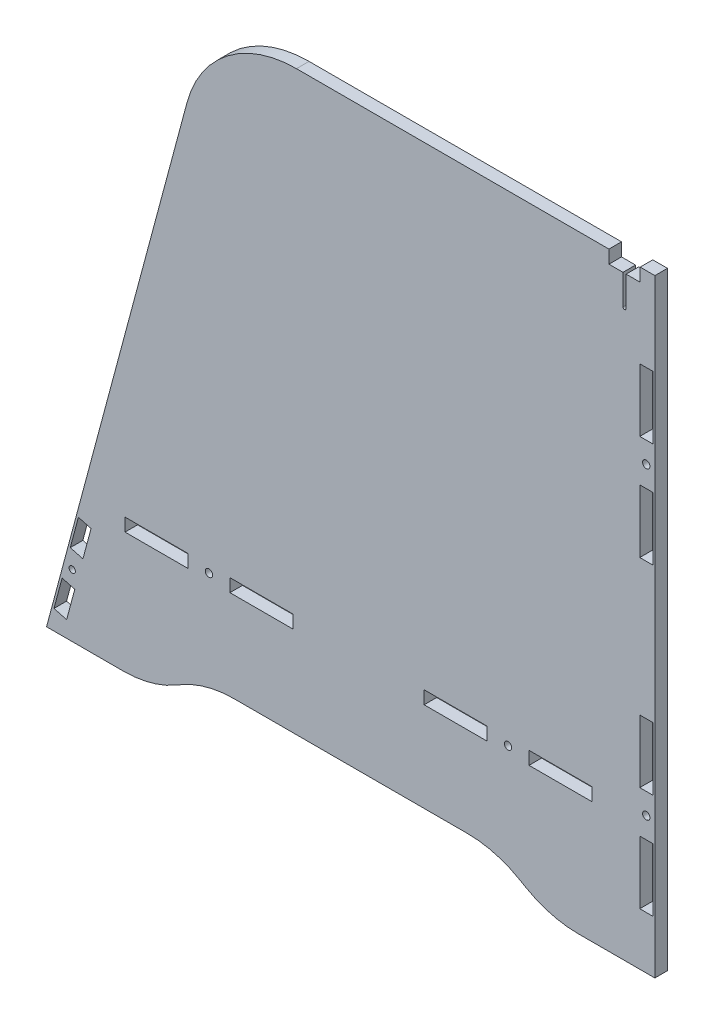
SolidWorks part; units mm, degrees
ref_plane "Plano frontal" through (0, 0, 0) normal (0, 0, 1) x (1, 0, 0)
ref_plane "Plano superior" through (0, 0, 0) normal (0, 1, 0) x (1, 0, 0)
ref_plane "Plano direito" through (0, 0, 0) normal (1, 0, 0) x (0, 0, -1)
sketch "Esboço1" plane through (0, 0, 0) normal (0, 0, 1) x (1, 0, 0)
  line L0 (125, -165) -> (75, -165)
  line L1 (75, -165) -> (49.0192, -150)
  line L2 (49.0192, -150) -> (-89.0192, -150)
  line L3 (-89.0192, -150) -> (-115, -165)
  line L4 (-115, -165) -> (-165, -165)
  line L5 (-165, -165) -> (-87.2947, 125)
  line L6 (-87.2947, 125) -> (125, 125)
  line L7 (125, 125) -> (125, -165)
  line L8 (-147.5833, -100) -> (125, -100) construction
  line L9 (-27.2947, 124) -> (65, 117.8) construction
  line L10 (125, -165) -> (-165, -165) construction
  line L11 (125, -165) -> (125, 125)
  line L12 (125, 125) -> (-165, 125) construction
  line L13 (-165, -165) -> (-165, 125) construction
  line L14 (-57.2947, 124) -> (-27.2947, 124) construction
  line L15 (-57.2947, 124) -> (-57.2947, 117.8) construction
  line L16 (-57.2947, 117.8) -> (-27.2947, 117.8) construction
  line L17 (-27.2947, 124) -> (-27.2947, 117.8) construction
  line L18 (65, 124) -> (95, 124) construction
  line L19 (65, 124) -> (65, 117.8) construction
  line L20 (65, 117.8) -> (95, 117.8) construction
  line L21 (95, 124) -> (95, 117.8) construction
  line L22 (-87.2947, 125) -> (-57.2947, 117.8) construction
  line L23 (95, 117.8) -> (125, 125) construction
  line L24 (95, -101) -> (95, -107.2)
  line L25 (15, -107.2) -> (45, -107.2)
  line L26 (65, -101) -> (95, -101)
  line L27 (65, -107.2) -> (95, -107.2)
  line L28 (15, -101) -> (15, -107.2)
  line L29 (45, -101) -> (45, -107.2)
  line L30 (15, -101) -> (45, -101)
  line L31 (-127.5833, -107.2) -> (-97.5833, -107.2)
  line L32 (65, -101) -> (65, -107.2)
  line L33 (45, -101) -> (65, -107.2) construction
  line L34 (-97.5833, -101) -> (-77.5833, -107.2) construction
  line L35 (-97.5833, -101) -> (-97.5833, -107.2)
  line L36 (-127.5833, -101) -> (-127.5833, -107.2)
  line L37 (-77.5833, -101) -> (-47.5833, -101)
  line L38 (-77.5833, -107.2) -> (-47.5833, -107.2)
  line L39 (-77.5833, -101) -> (-77.5833, -107.2)
  line L40 (-47.5833, -101) -> (-47.5833, -107.2)
  line L41 (-127.5833, -101) -> (-97.5833, -101)
  line L42 (117.8, 55) -> (124, 35) construction
  line L43 (117.8, 85) -> (124, 85)
  line L44 (117.8, 85) -> (117.8, 55)
  line L45 (117.8, 55) -> (124, 55)
  line L46 (124, 85) -> (124, 55)
  line L47 (117.8, 35) -> (124, 35)
  line L48 (117.8, 35) -> (117.8, 5)
  line L49 (117.8, 5) -> (124, 5)
  line L50 (124, 35) -> (124, 5)
  line L51 (117.8, -110) -> (117.8, -140)
  line L52 (117.8, -60) -> (124, -60)
  line L53 (117.8, -140) -> (124, -140)
  line L54 (124, -110) -> (124, -140)
  line L55 (124, -60) -> (124, -90)
  line L56 (117.8, -90) -> (124, -90)
  line L57 (117.8, -110) -> (124, -110)
  line L58 (117.8, -90) -> (124, -110) construction
  line L59 (117.8, -60) -> (117.8, -90)
  circle A0 centre (0, 0) radius 100 construction
  circle A1 centre (18.8526, 120.9) radius 1.75 construction
  circle A2 centre (-72.2947, 121.4) radius 1.75 construction
  circle A3 centre (110, 121.4) radius 1.75 construction
  circle A4 centre (-87.5833, -104.1) radius 1.75
  circle A5 centre (120.9, 45) radius 1.75
  circle A6 centre (55, -104.1) radius 1.75
  circle A7 centre (120.9, -100) radius 1.75
  dimension "D1" = 200
  dimension "D4" = 25
  dimension "D5" = 25
  dimension "D14" = 30
  dimension "D13" = 3.5
  dimension "D21" = 20
  dimension "D27" = 20
  dimension "D2" = 15
  dimension "D3" = 50
  dimension "D6" = 50
  dimension "D7" = 150
  dimension "D8" = 150
  dimension "D9" = 75
  dimension "D10" = 6.2
  dimension "D11" = 290
  dimension "D12" = 1
  dimension "D15" = 30
  dimension "D16" = 30
  dimension "D17" = 6.2
  dimension "D18" = 30
  dimension "D19" = 30
  dimension "D20" = 2
  dimension "D22" = 30
  dimension "D23" = 20
  dimension "D24" = 20
  dimension "D25" = 1
  dimension "D26" = 30
  dimension "D28" = 40
  dimension "D29" = 30
  dimension "D31" = 20
  dimension "D32" = 1
extrude "Ressalto-extrusão1" add sketch "Esboço1" along normal blind 6 contours L7 L6 L5 L4 L3 L2 L1 L0 A7 A6 A5 A4 A3 A2 A1 L59 L52 L55 L56 L47 L50 L49 L48 L36 L41 L35 L31 L28 L30 L29 L25 L14 L17 L16 L15 L18 L21 L20 region at (-2.1117, -21.9668, 0)
fillet "Filete1" radius 54 1 edges at (-87.2947, 125, 3)
fillet "Filete2" radius 50 4 edges at (75, -165, 3) (-115, -165, 3) (49.0192, -150, 3) (-89.0192, -150, 3)
sketch "Esboço2" plane through (0, 125, 0) normal (0, 1, 0) x (1, 0, 0)
  line L0 (-45.8591, 0) -> (125, 0) construction
  line L1 (103.1, 0) -> (118, 0)
  line L2 (103.1, 0) -> (103.1, -6)
  line L3 (103.1, -6) -> (118, -6)
  line L4 (118, 0) -> (118, -6)
  line L5 (-45.8591, -6) -> (125, -6) construction
  line L6 (103.3, 42) -> (103.3, -6) construction
  line L7 (117.8, 181) -> (117.8, 171) construction
  dimension "D1" = 0.2
  dimension "D2" = 0.2
extrude "Corte-extrusão1" cut sketch "Esboço2" against normal blind 6.25
sketch "Esboço3" plane through (0, 0, 6) normal (0, 0, 1) x (1, 0, 0)
  line L0 (110.55, 118.75) -> (110.55, 103.75) construction
  line L1 (103.1, 118.75) -> (118, 118.75) construction
  line L2 (109.8, 118.75) -> (109.8, 103.75)
  line L3 (111.3, 118.75) -> (111.3, 103.75)
  line L4 (109.8, 103.75) -> (111.3, 103.75)
  line L5 (111.3, 118.75) -> (109.8, 118.75)
  dimension "D1" = 15
  dimension "D2" = 0.75
  dimension "D3" = 0.75
extrude "Corte-extrusão2" cut sketch "Esboço3" against normal blind 10
fillet "Filete3" radius 0.75 2 edges at (111.3, 103.75, 3) (109.8, 103.75, 3)
sketch "Esboço4" plane through (0, 0, 6) normal (0, 0, 1) x (1, 0, 0)
  line L0 (-163.5313, -163.3824) -> (-148.017, -105.4824)
  line L2 (-128.3975, -165) -> (-165, -165) construction
  line L3 (-148.017, -105.4824) -> (-141.98, -107.1)
  line L4 (-141.98, -107.1) -> (-157.4942, -165)
  line L5 (-157.4942, -165) -> (-163.5313, -163.3824)
  line L6 (-165, -165) -> (-98.0191, 84.9762) construction
  line L7 (-127.4833, -107.1) -> (-141.88, -107.1) construction
  line L8 (-144.9985, -106.2912) -> (-160.5128, -164.1912) construction
  line L9 (-161.4607, -155.655) -> (-155.4237, -157.2726)
  line L10 (-157.5784, -141.1661) -> (-151.5414, -142.7837)
  line L11 (-153.6962, -126.6772) -> (-147.6591, -128.2948)
  line L12 (-149.8139, -112.1883) -> (-143.7768, -113.8059)
  circle A0 centre (-152.7556, -135.2412) radius 1.5
  dimension "D3" = 3
  dimension "D1" = 6.25
  dimension "D2" = 1
  dimension "D4" = 8
  dimension "D5" = 15
  dimension "D6" = 15
  dimension "D7" = 15
extrude "Corte-extrusão3" cut sketch "Esboço4" against normal blind 22 contours L8 L12 L0 L11 | L12 L8 L11 L4 | A0 L8 | L8 A0 | L8 L10 L0 L9 | L10 L8 L9 L4 region at (-158.0103, -148.8149, 6) region at (-154.9918, -149.6237, 6) region at (-150.2458, -119.8372, 6) region at (-147.2272, -120.646, 6) region at (-153.3706, -135.0764, 6) region at (-152.1407, -135.406, 6)
